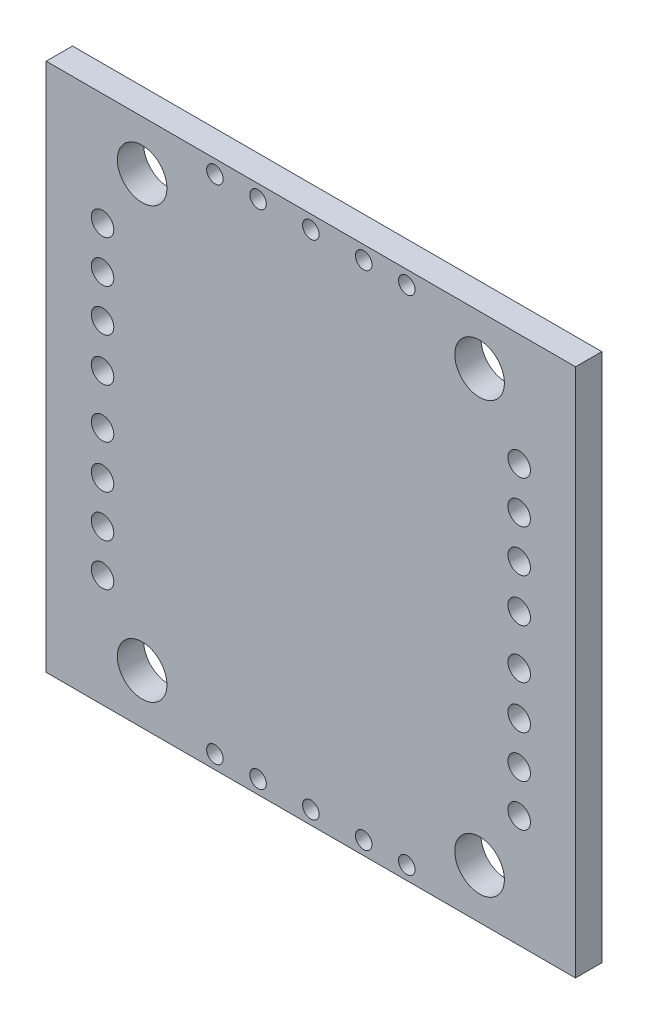
SolidWorks part; units mm, degrees
ref_plane "前视基准面" through (0, 0, 0) normal (0, 0, 1) x (1, 0, 0)
ref_plane "上视基准面" through (0, 0, 0) normal (0, 1, 0) x (1, 0, 0)
ref_plane "右视基准面" through (0, 0, 0) normal (1, 0, 0) x (0, 0, -1)
sketch "草图2" plane through (0, 0, 0) normal (0, 0, 1) x (1, 0, 0)
  line L1 (16, -16) -> (-16, -16)
  line L2 (16, -16) -> (16, 16)
  line L3 (16, 16) -> (-16, 16)
  line L4 (-16, -16) -> (-16, 16)
  line L5 (16, -16) -> (-16, 16) construction
  line L6 (16, 16) -> (-16, -16) construction
  point P0 (0, 0)
sketch "草图3" plane through (0, 0, 0) normal (0, 0, 1) x (1, 0, 0)
  line L0 (-16, 16) -> (-10.63, 16) construction
  line L1 (16, 16) -> (-16, 16) construction
  line L2 (-16, 13) -> (-13.84, 13) construction
  line L3 (16, -16) -> (-16, -16) construction
  line L4 (-16, 16) -> (-16, 8.4669) construction
  line L5 (-16, -16) -> (-16, 16) construction
  line L6 (-13.8441, 16) -> (-13.8441, 10.6) construction
  line L7 (16, -16) -> (16, 16) construction
  line L8 (-16, -16) -> (-16, -10.84) construction
  line L9 (-16, -10.84) -> (16, -10.84) construction
  line L10 (16, 16) -> (10.63, 16) construction
  line L11 (10.63, 16) -> (10.63, -16) construction
  line L12 (-13.8441, 10.6) -> (-13.8441, -10.35) construction
  line L13 (-10.63, -16) -> (-10.63, -13.18) construction
  line L14 (-13.8441, -10.35) -> (-11.3441, -10.35) construction
  line L15 (-6.2936, 13) -> (-6.2936, -16) construction
  line L16 (-16, 15.18) -> (-5.8, 15.18) construction
  line L17 (-5.8, 15.18) -> (-3.1939, 15.18) construction
  line L18 (6.2764, -16) -> (-6.2936, -16) construction
  line L20 (-5.8, 16) -> (-5.8, 15.18) construction
  line L21 (6.2764, -16) -> (6.2764, -14.16) construction
  line L22 (6.2764, -14.16) -> (-6.2936, -14.16) construction
  line L23 (-5.8, 15.18) -> (-3.1939, 15.18) construction
  line L27 (0, 16) -> (0, -16) construction
  line L28 (16, -16) -> (-16, -16)
  line L29 (16, -16) -> (16, 16)
  line L30 (16, 16) -> (-16, 16)
  line L31 (-16, -16) -> (-16, 16)
  line L32 (16, -16) -> (-16, 16) construction
  line L33 (16, 16) -> (-16, -16) construction
  line L34 (-16, 11.5) -> (-13.82, 11.5) construction
  line L35 (-11.3441, -10.35) -> (-11.3441, 10.6) construction
  line L36 (-11.3441, 10.6) -> (-13.8441, 10.6) construction
  line L37 (-13.8441, 10.6) -> (-13.8441, 7.982) construction
  line L38 (-13.82, 11.5) -> (-10.89, 11.5) construction
  line L39 (-13.8441, 7.982) -> (-11.3441, 7.982) construction
  line L40 (-13.8441, 7.982) -> (-13.8441, 5.364) construction
  line L41 (-16, 0) -> (16, 0) construction
  line L42 (-13.8441, 5.364) -> (-11.3441, 5.364) construction
  line L43 (-13.8441, 5.364) -> (-13.8441, 2.746) construction
  line L44 (-13.8441, 2.746) -> (-11.3441, 2.746) construction
  line L45 (-5.8, 15.18) -> (-3.68, 15.18) construction
  line L46 (-3.68, 15.18) -> (-1.48, 15.18) construction
  line L47 (-1.48, 15.18) -> (0.72, 15.18) construction
  circle A0 centre (-10.2, 13) radius 1.5
  circle A1 centre (10.2, 13) radius 1.5
  circle A2 centre (10.2, -13) radius 1.5
  circle A3 centre (-10.2, -13) radius 1.5
  circle A4 centre (-12.5941, 9.2172) radius 0.68
  circle A5 centre (-12.5941, 6.6641) radius 0.68
  circle A6 centre (-12.5941, 4.1109) radius 0.68
  circle A7 centre (-12.5941, 1.4923) radius 0.68
  circle A8 centre (-12.5941, -1.4923) radius 0.68
  circle A9 centre (-12.5941, -4.1109) radius 0.68
  circle A10 centre (-12.5941, -6.6641) radius 0.68
  circle A11 centre (-12.5941, -9.2172) radius 0.68
  circle A12 centre (12.5941, -9.2172) radius 0.68
  circle A13 centre (12.5941, -6.6641) radius 0.68
  circle A14 centre (12.5941, -4.1109) radius 0.68
  circle A15 centre (12.5941, -1.4923) radius 0.68
  circle A16 centre (12.5941, 1.4923) radius 0.68
  circle A17 centre (12.5941, 4.1109) radius 0.68
  circle A18 centre (12.5941, 6.6641) radius 0.68
  circle A19 centre (12.5941, 9.2172) radius 0.68
  circle A20 centre (-5.8, 15.18) radius 0.5
  circle A21 centre (0, 15.18) radius 0.5
  circle A22 centre (-3.1939, 15.18) radius 0.5
  circle A23 centre (3.1939, 15.18) radius 0.5
  circle A24 centre (5.8, 15.18) radius 0.5
  circle A25 centre (5.8, -15.18) radius 0.5
  circle A26 centre (3.1939, -15.18) radius 0.5
  circle A27 centre (0, -15.18) radius 0.5
  circle A28 centre (-3.1939, -15.18) radius 0.5
  circle A29 centre (-5.8, -15.18) radius 0.5
  point P22 (-10.63, 10.84)
  point P23 (10.63, 10.84)
  point P24 (-10.63, -10.84)
  point P25 (10.63, -10.84)
  point P30 (-10.2, 14.5)
  point P32 (-11.7, 13)
  point P34 (-8.7, 13)
  point P37 (-6.2238, 16)
  point P47 (0, 0)
  dimension "D1" = 3
  dimension "D9" = 10.2
  dimension "D11" = 0.82
  dimension "D2" = 1.5
  dimension "D3" = 4.3
  dimension "D4" = 2.16
  dimension "D5" = 5.4
  dimension "D6" = 2.18
  dimension "D7" = 20.95
  dimension "D8" = 2.5
  dimension "D10" = 0.82
extrude "凸台-拉伸5" add sketch "草图3" along normal blind 1.59
